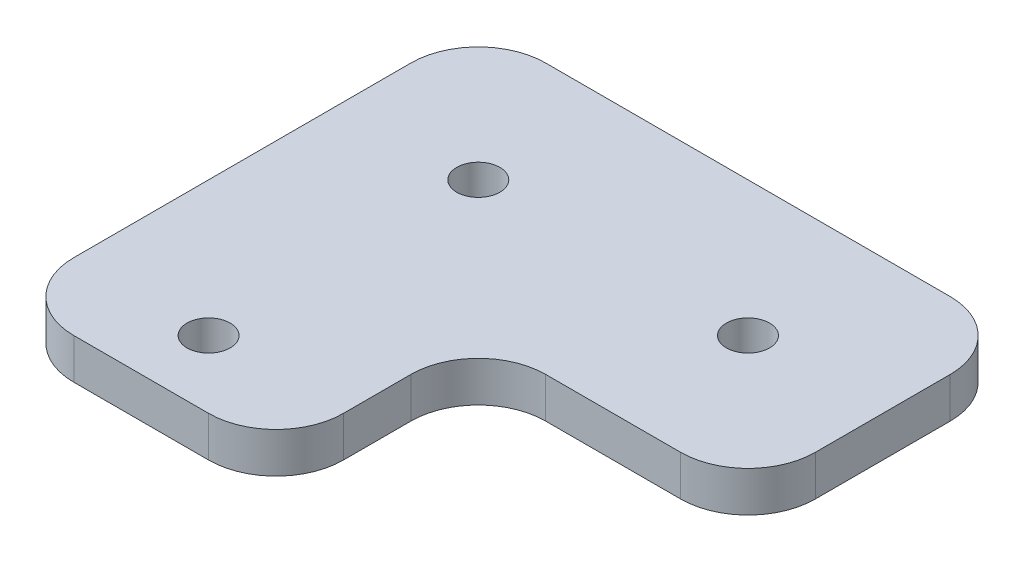
SolidWorks part; units mm, degrees
ref_plane "前视基准面" through (0, 0, 0) normal (0, 0, 1) x (1, 0, 0)
ref_plane "上视基准面" through (0, 0, 0) normal (0, 1, 0) x (1, 0, 0)
ref_plane "右视基准面" through (0, 0, 0) normal (1, 0, 0) x (0, 0, -1)
other "Configuration Table"
sketch "草图1" plane through (0, 0, 0) normal (0, 1, 0) x (1, 0, 0)
  line L0 (0, 0) -> (0, 35)
  line L1 (0, 35) -> (40, 35)
  line L2 (40, 35) -> (40, 15)
  line L4 (40, 15) -> (20, 15)
  line L5 (20, 15) -> (20, 0)
  line L6 (0, 0) -> (20, 0)
  circle A13 centre (30, 25) radius 1.6
  circle A14 centre (10, 25) radius 1.6
  circle A15 centre (10, 5) radius 1.6
  dimension "D8" = 10
  dimension "D5" = 3.2
  dimension "D6" = 3.2
  dimension "D7" = 3.2
  dimension "D1" = 20
  dimension "D2" = 20
  dimension "D3" = 35
  dimension "D4" = 20
  dimension "D10" = 10
  dimension "D11" = 20
  dimension "D12" = 10
  dimension "D13" = 20
  dimension "D9" = 10
extrude "凸台-拉伸1" add sketch "草图1" along normal blind 3
fillet "圆角1" radius 5 6 edges at (0, 1.5, 0) (20, 1.5, 0) (40, 1.5, -15) (40, 1.5, -35) (0, 1.5, -35) (20, 1.5, -15)
